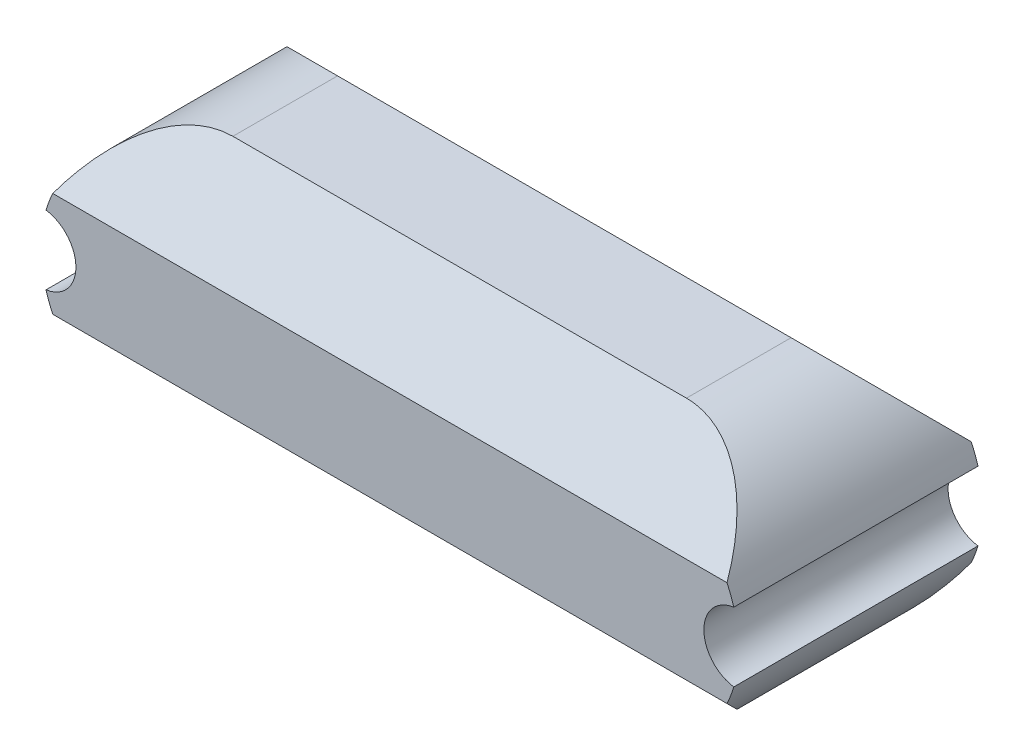
SolidWorks part; units mm, degrees
ref_plane "Ön Düzlem" through (0, 0, 0) normal (0, 0, 1) x (1, 0, 0)
ref_plane "Üst Düzlem" through (0, 0, 0) normal (0, 1, 0) x (1, 0, 0)
ref_plane "Sağ Düzlem" through (0, 0, 0) normal (1, 0, 0) x (0, 0, -1)
sketch "Çizim1" plane through (0, 0, 0) normal (0, 0, 1) x (1, 0, 0)
  line L1 (-50, 17.5) -> (50, 17.5)
  line L2 (-50, 17.5) -> (-50, -17.5)
  line L3 (-50, -17.5) -> (50, -17.5)
  line L4 (50, 17.5) -> (50, -17.5)
  line L5 (-50, 17.5) -> (50, -17.5) construction
  line L6 (-50, -17.5) -> (50, 17.5) construction
  point P0 (0, 0)
  dimension "D1" = 35
  dimension "D2" = 100
extrude "Yükseklik-Ekstrüzyon1" add sketch "Çizim1" along normal blind 35
fillet "Radyus1" radius 17.5 1 edges at (-50, 17.5, 17.5)
fillet "Radyus2" radius 17.5 1 edges at (-50, -17.5, 17.5)
fillet "Radyus3" radius 17.5 2 edges at (50, -17.5, 17.5) (50, 17.5, 17.5)
sketch "Çizim2" plane through (0, 0, 35) normal (0, 0, 1) x (1, 0, 0)
  circle A0 centre (-50, 0) radius 5
  circle A1 centre (50, 0) radius 5
  dimension "D1" = 10
  dimension "D2" = 10
extrude "Kes-Ekstrüzyon1" cut sketch "Çizim2" against normal through all
chamfer "Pah2" distance 10 angle 45 1 edges at (0, 17.5, 0) tangent propagation no
chamfer "Pah3" distance 10 angle 45 3 edges at (0, -17.5, 0) (0, -17.5, 35) (0, 17.5, 35) tangent propagation no
